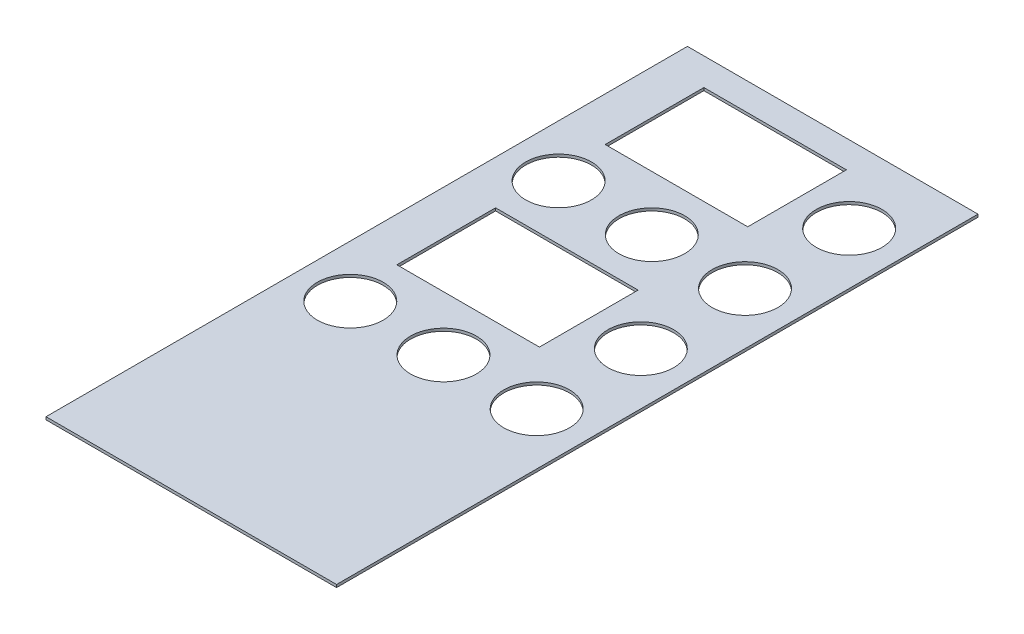
SolidWorks part; units mm, degrees
ref_plane "Спереди" through (0, 0, 0) normal (0, 0, 1) x (1, 0, 0)
ref_plane "Сверху" through (0, 0, 0) normal (0, 1, 0) x (1, 0, 0)
ref_plane "Справа" through (0, 0, 0) normal (1, 0, 0) x (0, 0, -1)
sketch "Эскиз1" plane through (0, 0, 0) normal (0, 1, 0) x (1, 0, 0)
  line L1 (-26.5, -58.5) -> (26.5, -58.5)
  line L2 (-26.5, -58.5) -> (-26.5, 58.5)
  line L3 (-26.5, 58.5) -> (26.5, 58.5)
  line L4 (26.5, -58.5) -> (26.5, 58.5)
  line L5 (-26.5, -58.5) -> (26.5, 58.5) construction
  line L6 (-26.5, 58.5) -> (26.5, -58.5) construction
  point P0 (0, 0)
  dimension "D1" = 117
  dimension "D2" = 53
extrude "Бобышка-Вытянуть1" add sketch "Эскиз1" along normal blind 0.5
sketch "Эскиз2" plane through (0, 0.5, 0) normal (0, 1, 0) x (1, 0, 0)
  line L0 (-26.5, 55.5) -> (26.5, 55.5) construction
  line L1 (-26.5, 58.5) -> (-26.5, -58.5) construction
  line L2 (26.5, -58.5) -> (26.5, 58.5) construction
  line L3 (26.5, 58.5) -> (-26.5, 58.5) construction
  line L4 (0, 58.5) -> (0, -58.5) construction
  line L5 (-18.5, 53.5) -> (7.5, 53.5)
  line L6 (-18.5, 53.5) -> (-18.5, 35.5)
  line L7 (-18.5, 35.5) -> (7.5, 35.5)
  line L8 (7.5, 53.5) -> (7.5, 35.5)
  line L9 (-18.5, 53.5) -> (7.5, 35.5) construction
  line L10 (-18.5, 35.5) -> (7.5, 53.5) construction
  line L11 (-26.5, -58.5) -> (26.5, -58.5) construction
  line L13 (-18.5, -2.5) -> (7.5, -2.5)
  line L14 (-18.5, -2.5) -> (-18.5, 15.5)
  line L15 (-18.5, 15.5) -> (7.5, 15.5)
  line L16 (7.5, -2.5) -> (7.5, 15.5)
  line L17 (-18.5, -2.5) -> (7.5, 15.5) construction
  line L18 (-18.5, 15.5) -> (7.5, -2.5) construction
  point P8 (-5.5, 44.5)
  point P17 (-5.5, 6.5)
  point P24 (7.5, 44.5)
  dimension "D1" = 3
  dimension "D2" = 2
  dimension "D3" = 18
  dimension "D4" = 26
  dimension "D5" = 5.5
  dimension "D6" = 18
  dimension "D7" = 20
sketch "Эскиз4" plane through (0, 0.5, 0) normal (0, 1, 0) x (1, 0, 0)
  line L0 (-26.5, 55.5) -> (26.5, 55.5) construction
  line L1 (-26.5, 58.5) -> (-26.5, -58.5) construction
  line L2 (26.5, -58.5) -> (26.5, 58.5) construction
  line L3 (26.5, 58.5) -> (-26.5, 58.5) construction
  line L4 (0, 58.5) -> (0, -58.5) construction
  line L5 (-26.5, -58.5) -> (26.5, -58.5) construction
  circle A0 centre (17, 44.5) radius 6
  circle A1 centre (17, 25.5) radius 6
  circle A2 centre (17, 6.5) radius 6
  circle A3 centre (17, -12.5) radius 6
  circle A4 centre (0, 25.5) radius 6
  circle A5 centre (-17, 25.5) radius 6
  circle A6 centre (0, -12.5) radius 6
  circle A7 centre (-17, -12.5) radius 6
  dimension "D4" = 19
  dimension "отверстие под кнопку" = 12
  dimension "D5" = 19
  dimension "D1" = 3
  dimension "D2" = 11
  dimension "D3" = 17
  dimension "D6" = 19
  dimension "D7" = 17
  dimension "D8" = 17
extrude "Вырез-Вытянуть1" cut sketch "Эскиз2" against normal through all
extrude "Вырез-Вытянуть2" cut sketch "Эскиз4" against normal through all
